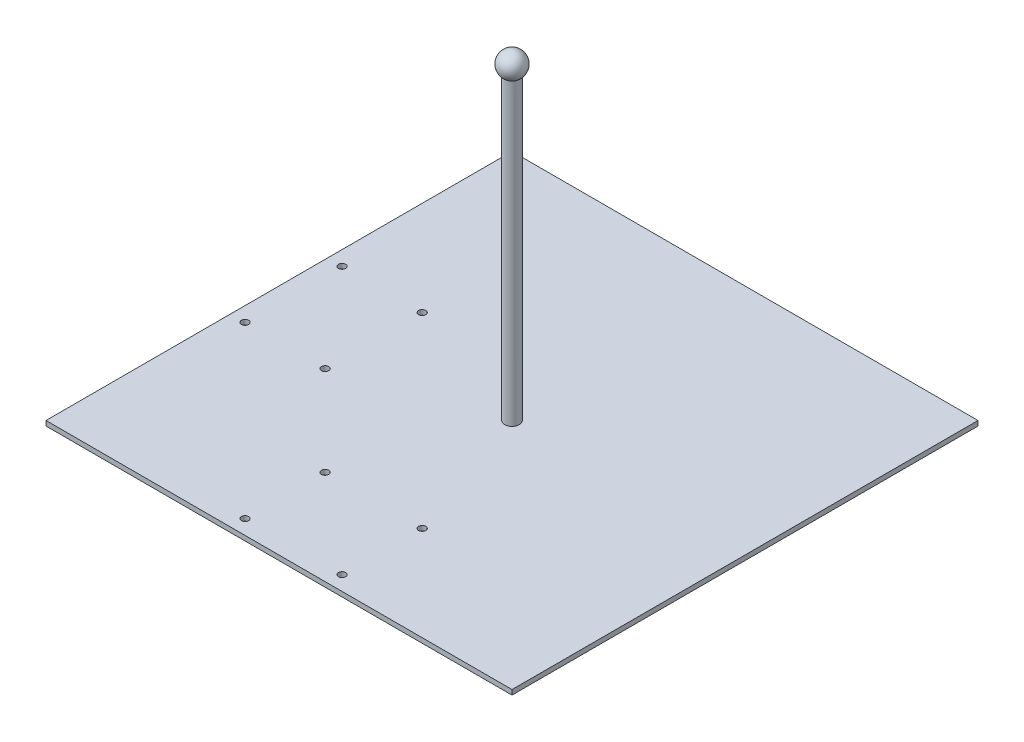
SolidWorks part; units mm, degrees
ref_plane "Front Plane" through (0, 0, 0) normal (0, 0, 1) x (1, 0, 0)
ref_plane "Top Plane" through (0, 0, 0) normal (0, 1, 0) x (1, 0, 0)
ref_plane "Right Plane" through (0, 0, 0) normal (1, 0, 0) x (0, 0, -1)
sketch "Sketch1" plane through (0, 0, 0) normal (0, 1, 0) x (1, 0, 0)
  line L1 (-304.8, -304.8) -> (304.8, -304.8)
  line L2 (-304.8, -304.8) -> (-304.8, 304.8)
  line L3 (-304.8, 304.8) -> (304.8, 304.8)
  line L4 (304.8, -304.8) -> (304.8, 304.8)
  dimension "D1" = 609.6
  dimension "D2" = 609.6
  dimension "D3" = 304.8
  dimension "D4" = 304.8
extrude "Boss-Extrude1" add sketch "Sketch1" along normal blind 6.35 contours L2 L3 L4 L1
hole_wizard "3/8 (0.375) Diameter Hole1" positions "Sketch2" profile "Sketch3" hole size "3/8" standard "ANSI Inch"
sketch "Sketch2" plane through (0, 6.35, 0) normal (0, 1, 0) x (1, 0, 0)
  line L1 (-304.8, -304.8) -> (-304.8, 304.8) construction
  line L3 (-304.8, -304.8) -> (304.8, -304.8) construction
  point P0 (-63.5, -285.75)
  point P2 (63.5, -285.75)
  point P4 (-285.75, 63.5)
  point P6 (-285.75, -63.5)
  point P17 (-304.8, 0)
  point P33 (-63.5, -180.975)
  point P35 (63.5, -180.975)
  point P37 (-180.975, -63.5)
  point P39 (-180.975, 63.5)
  dimension "D1" = 63.5
  dimension "D2" = 127
  dimension "D3" = 19.05
  dimension "D4" = 19.05
  dimension "D5" = 127
  dimension "D6" = 63.5
  dimension "D7" = 104.775
  dimension "D8" = 104.775
sketch "Sketch3" plane through (-63.5, 6.35, 285.75) normal (1, 0, 0) x (0, 0, 1)
  line L0 (0, 0) -> (0, 14.5456)
  line L1 (0, 14.5456) -> (4.7625, 11.684)
  line L2 (4.7625, 11.684) -> (4.7625, 0)
  line L5 (4.7625, 0) -> (0, 0)
  line L10 (0, 14.5456) -> (-4.7625, 11.684) construction
  line L11 (0, -6.35) -> (0, 107.95) construction
  dimension "Hole Dia." = 9.525
  dimension "Hole Depth" = 11.684
  dimension "Drill Angle" = 118
sketch "Sketch4" plane through (0, 6.35, 0) normal (0, 1, 0) x (1, 0, 0)
  circle A0 centre (0, 0) radius 9.525
  dimension "D1" = 19.05
extrude "Boss-Extrude2" add sketch "Sketch4" along normal blind 391.16
ref_axis "Axis1" through (0, 599.8237, 0) along (0, -1, 0)
sketch "Sketch5" plane through (0, 0, 0) normal (0, 0, 1) x (1, 0, 0)
  line L0 (0, 426.085) -> (0, 394.335)
  arc A0 (0, 426.085) -> (0, 394.335) centre (0, 410.21) ccw
  dimension "D1" = 31.75
revolve "Revolve3" add sketch "Sketch5" angle 360 about axis through (0, 599.8237, 0) along (0, -1, 0)
